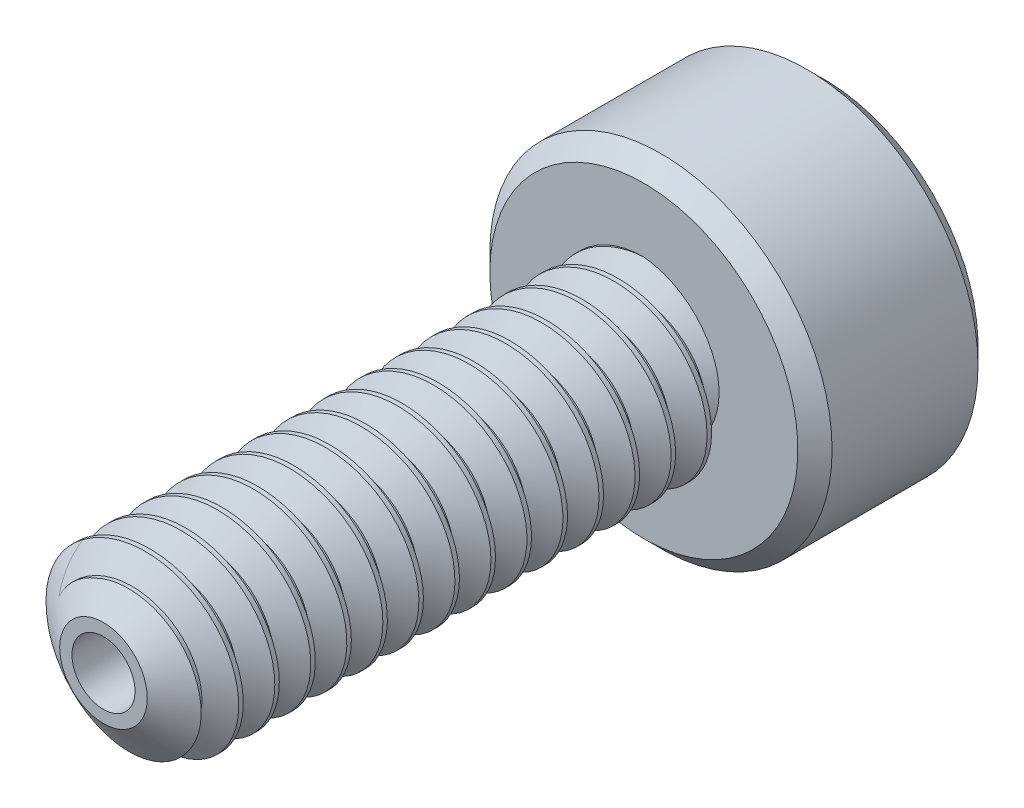
SolidWorks part; units mm, degrees
other "DetailItem1"
ref_plane "Front Plane" through (0, 0, 0) normal (0, 0, 1) x (1, 0, 0)
ref_plane "Top Plane" through (0, 0, 0) normal (0, 1, 0) x (1, 0, 0)
ref_plane "Right Plane" through (0, 0, 0) normal (1, 0, 0) x (0, 0, -1)
sketch "Sketch1" plane through (0, 0, 0) normal (0, 0, 1) x (1, 0, 0)
  circle A0 centre (0, 0) radius 1
  dimension "OD" = 2
extrude "Extrude1" add sketch "Sketch1" against normal blind 6
sketch "Sketch2" plane through (0, 0, 0) normal (0, 0, 1) x (1, 0, 0)
  circle A0 centre (0, 0) radius 1 construction
  circle A1 centre (0, 0) radius 1
curve "Helix/Spiral1" pitch 0.4 height 6.4 radius 1 centre (0, 0, 0) axis (0, 0, -1) start towards (0, 1, 0) parameters "pitch"=0.4
sketch "Sketch3" plane through (0, 0, 0) normal (1, 0, 0) x (0, 0, -1)
  line L0 (-0.35, 1) -> (-0.2, 0.7402)
  line L1 (-0.2, 0.7402) -> (-0.15, 0.7402)
  line L2 (-0.15, 0.7402) -> (0, 1)
  line L3 (-0.35, 1) -> (0, 1)
  line L4 (-0.175, 1) -> (-0.175, 0.7402) construction
  line L5 (-0.275, 0.8701) -> (-0.075, 0.8701) construction
  line L6 (0, 1) -> (0, -1) construction
  dimension "D1" = 0.05
  dimension "D2" = 0.2
  dimension "D3" = 60
sweep "Cut-Sweep1" cut profiles "Sketch3" path "Helix/Spiral1" align with end faces yes
sketch "Sketch4" plane through (0, 0, 0) normal (1, 0, 0) x (0, 0, -1)
  line L0 (0.3598, 1) -> (0, 0.4862)
  line L1 (0, 0.4862) -> (0, 1)
  line L2 (0.3598, 1) -> (0, 1)
  line L3 (-0.35, 1) -> (0, 1) construction
  line L4 (0, 0) -> (7.0209, 0) construction
  dimension "D1" = 55
  dimension "D2" = 0.254
revolve "Cut-Revolve1" cut sketch "Sketch4" angle 360 about L4
sketch "Sketch6" plane through (0, 0, -6) normal (0, 0, -1) x (-1, 0, 0)
  circle A0 centre (0, 0) radius 1.9
  dimension "head dia" = 3.8
extrude "Extrude2" add sketch "Sketch6" along normal blind 2
sketch "Sketch7" plane through (0, 0, -8) normal (0, 0, -1) x (-1, 0, 0)
  line L1 (0, 0.866) -> (-0.75, 0.433)
  line L2 (-0.75, 0.433) -> (-0.75, -0.433)
  line L3 (-0.75, -0.433) -> (0, -0.866)
  line L4 (0, -0.866) -> (0.75, -0.433)
  line L5 (0.75, -0.433) -> (0.75, 0.433)
  line L6 (0.75, 0.433) -> (0, 0.866)
  circle A0 centre (0, 0) radius 0.75 construction
  dimension "hex dia" = 1.5
extrude "Cut-Extrude1" cut sketch "Sketch7" against normal blind 1.125
sketch "Sketch8" plane through (0, 0, -8) normal (0, 0, -1) x (-1, 0, 0)
  circle A0 centre (0, 0) radius 0.866
extrude "Cut-Extrude2" cut sketch "Sketch8" against normal through all draft 45
chamfer "Chamfer1" distance 0.19 angle 45 2 edges at (-1.9, 0, -8) (-1.9, 0, -6)
sketch "Sketch10" plane through (0, 0, -6) normal (0, 0, 1) x (1, 0, 0)
  circle A1 centre (0, 0) radius 1
  circle A2 centre (0, 0) radius 1
  dimension "D1" = 0
ref_plane "Plane1" through (0, 0, 0) normal (0, 0, 1) x (1, 0, 0)
extrude "partial thread" [suppressed] add sketch "Sketch10" along normal up to surface (12.7 mm away) separate body up to plane "Plane1"
chamfer "Chamfer2" [suppressed] distance 0.04 angle 45
combine bodies "Combine1" [suppressed] operation type add bodies to combine 107 108
sketch "Sketch9" plane through (0, 0, 0) normal (1, 0, 0) x (0, 0, -1)
  line L0 (0, 1) -> (0, -1) construction
  line L1 (1, 1) -> (1, -1) construction
  dimension "D1" = 1
sketch "Sketch11" plane through (0, 0, 0) normal (0, 0, 1) x (1, 0, 0)
  circle A0 centre (0, 0) radius 0.35
  dimension "Vent Dia" = 0.7
extrude "Cut-Extrude3" cut sketch "Sketch11" against normal through all
equation "\"D3@Helix/Spiral1\" = \"screw length@Extrude1\"+\"pitch@Helix/Spiral1\""
equation "\"D1@Sketch3\" = \"pitch@Helix/Spiral1\"*.125"
equation "\"D2@Sketch3\" = \"pitch@Helix/Spiral1\"*.5"
equation "\"D1@Cut-Extrude1\" = \"hex dia@Sketch7\"*.75"
equation "\"D1@Chamfer1\" = \"head dia@Sketch6\"*.05"
equation "\"D1@Sketch9\" = \"pitch@Helix/Spiral1\"*2.5"
equation "\"D1@Chamfer2\"=\"OD@Sketch1\"*.02"
